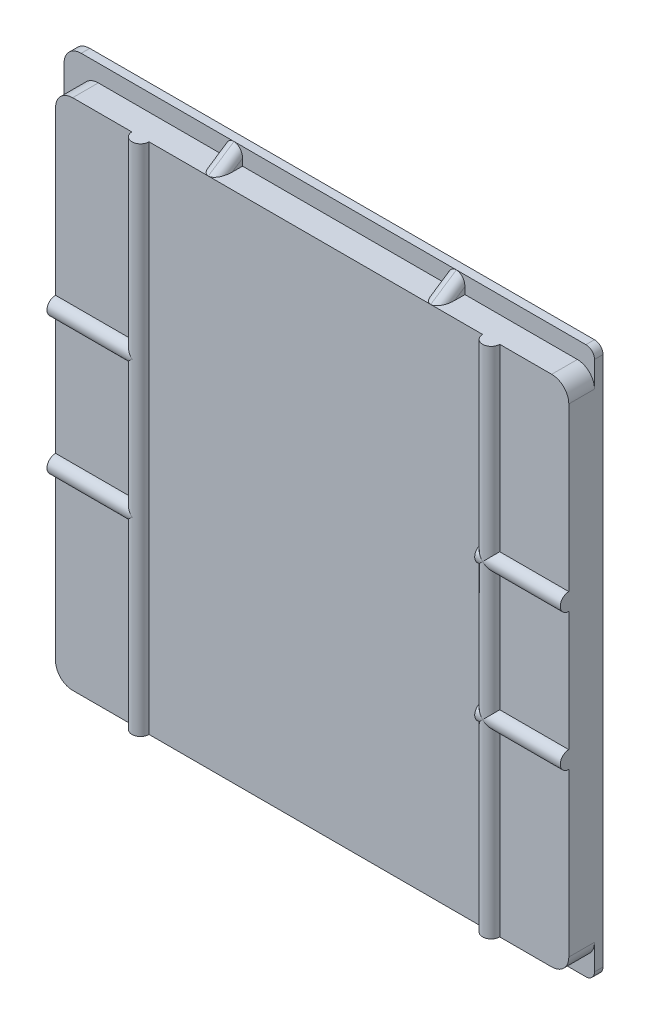
SolidWorks part; units mm, degrees
ref_plane "Front Plane" through (0, 0, 0) normal (0, 0, 1) x (1, 0, 0)
ref_plane "Top Plane" through (0, 0, 0) normal (0, 1, 0) x (1, 0, 0)
ref_plane "Right Plane" through (0, 0, 0) normal (1, 0, 0) x (0, 0, -1)
sketch "Sketch1" plane through (0, 0, 0) normal (0, 0, 1) x (1, 0, 0)
  line L1 (-274.292, 30.5164) -> (25.708, 30.5164)
  line L2 (-284.292, 20.5164) -> (-284.292, -279.4836)
  line L3 (-274.292, -289.4836) -> (25.708, -289.4836)
  line L4 (35.708, 20.5164) -> (35.708, -279.4836)
  arc A0 (25.708, -289.4836) -> (35.708, -279.4836) centre (25.708, -279.4836) ccw
  arc A1 (-284.292, -279.4836) -> (-274.292, -289.4836) centre (-274.292, -279.4836) ccw
  arc A2 (25.708, 30.5164) -> (35.708, 20.5164) centre (25.708, 20.5164) cw
  arc A3 (-274.292, 30.5164) -> (-284.292, 20.5164) centre (-274.292, 20.5164) ccw
  point P6 (35.708, -289.4836)
  point P11 (35.708, 30.5164)
  point P14 (-284.292, 30.5164)
  dimension "D3" = 10
  dimension "D1" = 320
  dimension "D2" = 320
extrude "Boss-Extrude1" add sketch "Sketch1" along normal blind 5
sketch "Sketch2" plane through (0, 0, 5) normal (0, 0, 1) x (1, 0, 0)
  line L0 (25.708, 30.5164) -> (-274.292, 30.5164) construction
  line L1 (-264.292, 20.5164) -> (15.708, 20.5164)
  line L2 (-274.292, 10.5164) -> (-274.292, -269.4836)
  line L3 (-264.292, -279.4836) -> (15.708, -279.4836)
  line L4 (25.708, 10.5164) -> (25.708, -269.4836)
  line L5 (-284.292, 20.5164) -> (-284.292, -279.4836) construction
  line L6 (35.708, -279.4836) -> (35.708, 20.5164) construction
  line L7 (-274.292, -289.4836) -> (25.708, -289.4836) construction
  arc A0 (-274.292, -269.4836) -> (-264.292, -279.4836) centre (-264.292, -269.4836) ccw
  arc A1 (15.708, -279.4836) -> (25.708, -269.4836) centre (15.708, -269.4836) ccw
  arc A2 (15.708, 20.5164) -> (25.708, 10.5164) centre (15.708, 10.5164) cw
  arc A3 (-264.292, 20.5164) -> (-274.292, 10.5164) centre (-264.292, 10.5164) ccw
  dimension "D5" = 10
  dimension "D1" = 10
  dimension "D2" = 10
  dimension "D3" = 10
  dimension "D4" = 10
extrude "Boss-Extrude2" add sketch "Sketch2" along normal blind 15
ref_plane "Plane1" through (-60, 0, 0) normal (1, 0, 0) x (0, 0, -1)
sketch "Sketch3" plane through (-60, 0, 0) normal (1, 0, 0) x (0, 0, -1)
  line L0 (-20, 20.5164) -> (-5, 20.5164)
  line L1 (-5, 20.5164) -> (-5, 30.5164)
  line L2 (-5, 30.5164) -> (-20, 20.5164)
extrude "Boss-Extrude3" add sketch "Sketch3" along normal blind 10
fillet "Fillet1" radius 5 2 edges at (-60, 25.5164, 12.5) (-50, 25.5164, 12.5)
ref_plane "Plane2" through (-180, 0, 0) normal (1, 0, 0) x (0, 0, -1)
sketch "Sketch4" plane through (-180, 0, 0) normal (1, 0, 0) x (0, 0, -1)
  line L0 (-20, 20.5164) -> (-5, 20.5164)
  line L1 (-5, 20.5164) -> (-5, 30.5164)
  line L2 (-5, 30.5164) -> (-20, 20.5164)
extrude "Boss-Extrude7" add sketch "Sketch4" against normal blind 10
sketch "Sketch9" plane through (-180, 0, 0) normal (1, 0, 0) x (0, 0, -1)
  line L0 (-20, -279.4836) -> (-5, -279.4836)
  line L1 (-5, -279.4836) -> (-5, -289.4836)
  line L2 (-5, -289.4836) -> (-20, -279.4836)
extrude "Boss-Extrude8" add sketch "Sketch9" against normal blind 10
sketch "Sketch10" plane through (-60, 0, 0) normal (1, 0, 0) x (0, 0, -1)
  line L0 (-20, -279.4836) -> (-5, -279.4836)
  line L1 (-5, -279.4836) -> (-5, -289.4836)
  line L2 (-5, -279.4836) -> (-5, -289.4836) construction
  line L3 (-20, -279.4836) -> (-5, -289.4836) construction
  line L4 (-5, -289.4836) -> (-20, -279.4836)
extrude "Boss-Extrude9" add sketch "Sketch10" along normal blind 10
fillet "Fillet5" radius 5 6 edges at (-50, -284.4836, 12.5) (-180, -284.4836, 12.5) (-60, -284.4836, 12.5) (-190, -284.4836, 12.5) (-190, 25.5164, 12.5) (-180, 25.5164, 12.5)
sketch "Sketch12" plane through (0, -279.4836, 0) normal (0, -1, 0) x (1, 0, 0)
  line L0 (-264.292, 20) -> (-185, 20) construction
  line L1 (-55, 20) -> (15.708, 20) construction
  line L2 (-229.646, 20) -> (-219.646, 20)
  line L3 (-24.646, 20) -> (-14.646, 20)
  arc A0 (-219.646, 20) -> (-229.646, 20) centre (-224.646, 20) ccw
  arc A1 (-14.646, 20) -> (-24.646, 20) centre (-19.646, 20) ccw
extrude "Boss-Extrude10" add sketch "Sketch12" against normal blind 300
sketch "Sketch13" plane through (-274.292, 0, 0) normal (-1, 0, 0) x (0, 0, 1)
  line L0 (20, 20.5164) -> (20, -279.4836) construction
  line L1 (20, 10.5164) -> (20, -269.4836) construction
  line L4 (20, -84.4836) -> (20, -94.4836)
  line L5 (20, -164.4836) -> (20, -174.4836)
  arc A0 (20, -94.4836) -> (20, -84.4836) centre (20, -89.4836) ccw
  arc A1 (20, -174.4836) -> (20, -164.4836) centre (20, -169.4836) ccw
  dimension "D1" = 80
extrude "Boss-Extrude12" add sketch "Sketch13" against normal blind 50
sketch "Sketch15" plane through (25.708, 0, 0) normal (1, 0, 0) x (0, 0, -1)
  line L0 (-20, 20.5164) -> (-20, -279.4836) construction
  line L1 (-20, -269.4836) -> (-20, 10.5164) construction
  line L2 (-20, 10.5164) -> (-5, 10.5164) construction
  line L3 (-20, -84.4836) -> (-20, -94.4836)
  line L4 (-20, -164.4836) -> (-20, -174.4836)
  arc A0 (-20, -84.4836) -> (-20, -94.4836) centre (-20, -89.4836) ccw
  arc A1 (-20, -164.4836) -> (-20, -174.4836) centre (-20, -169.4836) ccw
  dimension "D1" = 80
  dimension "D2" = 100
extrude "Boss-Extrude13" add sketch "Sketch15" against normal blind 50
sketch "Sketch16" plane through (0, 0, 0) normal (0, 0, -1) x (-1, 0, 0)
  line L0 (-35.708, -279.4836) -> (-35.708, 20.5164) construction
  line L1 (14.292, 10.5164) -> (264.292, 10.5164)
  line L2 (14.292, 10.5164) -> (14.292, -69.4836)
  line L3 (14.292, -269.4836) -> (264.292, -269.4836)
  line L4 (264.292, 10.5164) -> (264.292, -269.4836)
  line L5 (-25.708, 30.5164) -> (274.292, 30.5164) construction
  line L6 (14.292, -69.4836) -> (-15.708, -69.4836)
  line L8 (14.292, -189.4836) -> (-15.708, -189.4836)
  line L9 (-15.708, -69.4836) -> (-15.708, -189.4836)
  line L10 (274.292, -289.4836) -> (-25.708, -289.4836) construction
  line L11 (14.292, -189.4836) -> (14.292, -269.4836)
  dimension "D1" = 250
  dimension "D2" = 280
  dimension "D3" = 50
  dimension "D4" = 100
  dimension "D5" = 100
  dimension "D6" = 20
  dimension "D7" = 20
extrude "Cut-Extrude1" cut sketch "Sketch16" against normal blind 12
fillet "Fillet7" radius 5 8 edges at (-264.292, -269.4836, 6) (-14.292, -269.4836, 6) (-14.292, -189.4836, 6) (15.708, -189.4836, 6) (15.708, -69.4836, 6) (-14.292, -69.4836, 6) (-14.292, 10.5164, 6) (-264.292, 10.5164, 6)
fillet "Fillet8" radius 3 16 edges at (-15.7565, -268.0191, 12) (-14.292, -229.4836, 12) (-12.8275, -190.9481, 12) (0.708, -189.4836, 12) (14.2435, -188.0191, 12) (15.708, -129.4836, 12) (14.2435, -70.9481, 12) (0.708, -69.4836, 12) (-12.8275, -68.0191, 12) (-14.292, -29.4836, 12) (-15.7565, 9.0519, 12) (-139.292, 10.5164, 12) (-262.8275, 9.0519, 12) (-264.292, -129.4836, 12) (-262.8275, -268.0191, 12) (-139.292, -269.4836, 12)
sketch "Sketch17" plane through (0, 0, 0) normal (0, 0, -1) x (-1, 0, 0)
  line L0 (274.292, -289.4836) -> (-25.708, -289.4836) construction
  line L1 (-35.708, 30.5164) -> (-25.708, 30.5164)
  line L2 (-35.708, 30.5164) -> (-35.708, -289.4836)
  line L3 (-35.708, -289.4836) -> (-25.708, -289.4836)
  line L4 (-25.708, 30.5164) -> (-25.708, -289.4836)
  dimension "D1" = 10
extrude "Cut-Extrude2" cut sketch "Sketch17" against normal blind 10
fillet "Fillet9" radius 5 2 edges at (25.708, -289.4836, 2.5) (25.708, 30.5164, 2.5)
sketch "Sketch18" plane through (0, 0, 0) normal (0, 0, -1) x (-1, 0, 0)
  line L0 (14.292, 5.5164) -> (14.292, -64.4836) construction
  line L1 (14.292, -64.4836) -> (14.292, 5.5164) construction
  line L2 (-10.708, -69.4836) -> (9.292, -69.4836) construction
  line L3 (-10.708, -189.4836) -> (9.292, -189.4836) construction
  line L4 (14.292, -194.4836) -> (14.292, -264.4836) construction
  circle A0 centre (4.292, -4.4836) radius 2.5
  circle A1 centre (-15.508, -29.4836) radius 2.5
  circle A2 centre (4.292, -54.4836) radius 2.5
  circle A3 centre (4.292, -204.4836) radius 2.5
  circle A4 centre (-13.2584, -229.4836) radius 2.5
  circle A5 centre (4.292, -254.4836) radius 2.5
  point P0 (4.292, -54.4836)
  point P1 (4.292, -4.4836)
  point P2 (-15.508, -29.4836)
  point P15 (4.292, -204.4836)
  point P16 (4.292, -254.4836)
  point P17 (-13.2584, -229.4836)
  dimension "D7" = 5
  dimension "D8" = 50
  dimension "D1" = 10
  dimension "D2" = 10
  dimension "D3" = 25
  dimension "D4" = 50
  dimension "D5" = 29.8
  dimension "D6" = 15
  dimension "D9" = 25
  dimension "D10" = 15
  dimension "D11" = 10
  dimension "D12" = 10
extrude "Cut-Extrude3" cut sketch "Sketch18" against normal blind 10
